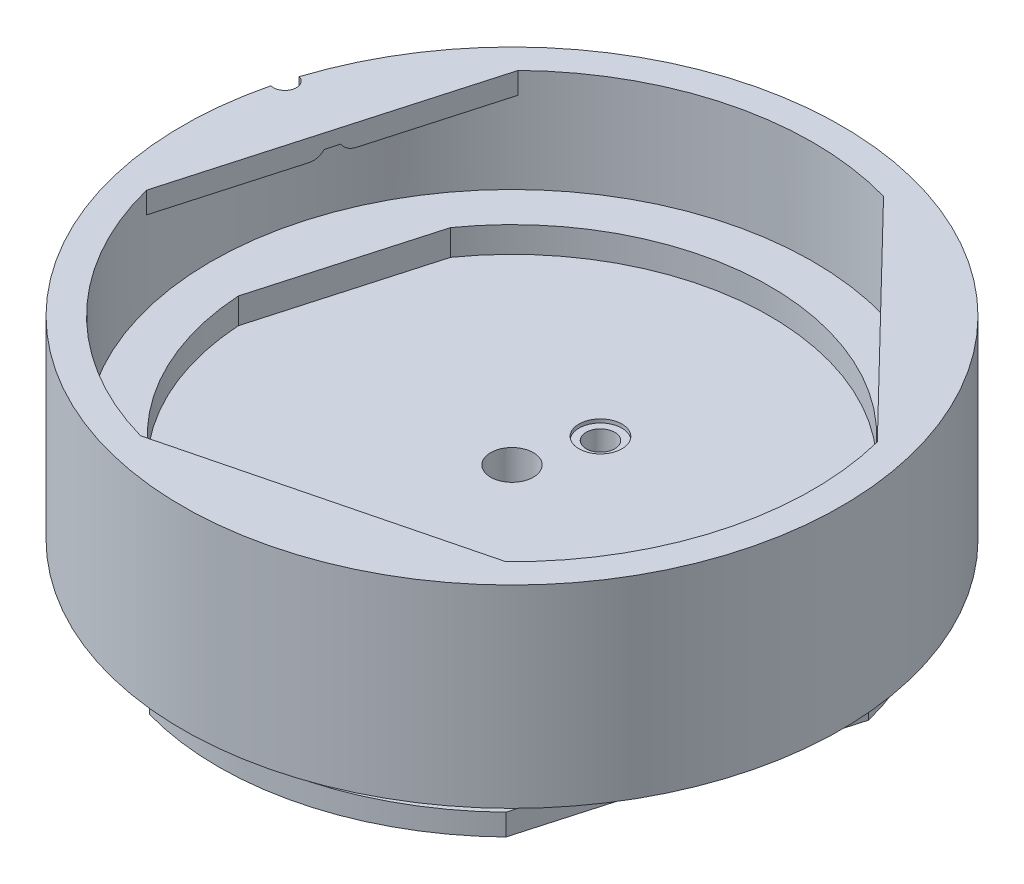
SolidWorks part; units mm, degrees
ref_plane "Front" through (0, 0, 0) normal (0, 0, 1) x (1, 0, 0)
ref_plane "Top" through (0, 0, 0) normal (0, 1, 0) x (1, 0, 0)
ref_plane "Right" through (0, 0, 0) normal (1, 0, 0) x (0, 0, -1)
sketch "Sketch1" plane through (0, 0, 0) normal (0, 1, 0) x (1, 0, 0)
  circle A0 centre (0, 0) radius 20.5
extrude "Boss-Extrude1" add sketch "Sketch1" along normal blind 1.5
sketch "Sketch2" plane through (0, 1.5, 0) normal (0, 1, 0) x (1, 0, 0)
  line L0 (-12.1923, 12.5538) -> (-12.889, 13.2712)
  line L1 (-16.9681, -4.2819) -> (-17.9377, -4.5266)
  line L2 (16.9681, 4.2819) -> (17.9377, 4.5266)
  line L3 (4.7758, 16.8357) -> (5.0487, 17.7978)
  line L4 (-4.7758, -16.8357) -> (-5.0487, -17.7978)
  line L5 (12.1923, -12.5538) -> (12.889, -13.2712)
  line L6 (-14.2824, 14.7059) -> (5.5945, 19.7219)
  line L7 (19.8769, 5.016) -> (14.2824, -14.7059)
  line L8 (-19.8769, -5.016) -> (-5.5945, -19.7219)
  line L9 (0, 0) -> (-14.2824, 14.7059) construction
  arc A0 (-19.8769, -5.016) -> (-5.5945, -19.7219) centre (0, 0) ccw
  arc A1 (-12.889, 13.2712) -> (-17.9377, -4.5266) centre (0, 0) ccw
  arc A2 (-12.1923, 12.5538) -> (-16.9681, -4.2819) centre (0, 0) ccw
  arc A3 (17.9377, 4.5266) -> (5.0487, 17.7978) centre (0, 0) ccw
  arc A4 (16.9681, 4.2819) -> (4.7758, 16.8357) centre (0, 0) ccw
  arc A5 (-5.0487, -17.7978) -> (12.889, -13.2712) centre (0, 0) ccw
  arc A6 (-4.7758, -16.8357) -> (12.1923, -12.5538) centre (0, 0) ccw
  arc A7 (14.2824, -14.7059) -> (19.8769, 5.016) centre (0, 0) ccw
  arc A8 (5.5945, 19.7219) -> (-14.2824, 14.7059) centre (0, 0) ccw
  point P13 (0, 0)
  dimension "D2" = 3
  dimension "D1" = 60
extrude "Cut-Extrude1" cut sketch "Sketch2" against normal blind 11
sketch "Sketch3" plane through (0, 1.5, 0) normal (0, 1, 0) x (1, 0, 0)
  circle A1 centre (0, 0) radius 17.5
extrude "Boss-Extrude2" add sketch "Sketch3" along normal blind 2
sketch "Sketch4" plane through (0, 3.5, 0) normal (0, 1, 0) x (1, 0, 0)
  circle A1 centre (0, 0) radius 23
extrude "Boss-Extrude3" add sketch "Sketch4" along normal blind 1
sketch "Sketch5" plane through (0, 4.5, 0) normal (0, 1, 0) x (1, 0, 0)
  circle A0 centre (0, 0) radius 23
  circle A1 centre (0, 0) radius 21
extrude "Boss-Extrude4" add sketch "Sketch5" along normal blind 11
sketch "Sketch6" plane through (0, 15.5, 0) normal (0, 1, 0) x (1, 0, 0)
  line L0 (0, 0) -> (-4.4043, 17.4529) construction
  line L2 (0, 0) -> (17.3168, -4.9122) construction
  line L5 (0, 0) -> (-12.9125, -12.5407) construction
  line L6 (14.6308, -15.0646) -> (-5.7309, -20.2029)
  line L7 (-20.3617, -5.1383) -> (-14.6308, 15.0646)
  line L8 (5.7309, 20.2029) -> (20.3617, 5.1383)
  circle A1 centre (0, 0) radius 23
  arc A4 (14.6308, -15.0646) -> (20.3617, 5.1383) centre (0, 0) ccw
  arc A5 (-20.3617, -5.1383) -> (-5.7309, -20.2029) centre (0, 0) ccw
  arc A6 (5.7309, 20.2029) -> (-14.6308, 15.0646) centre (0, 0) ccw
  point P14 (0, 0)
  point P18 (0, 0)
  point P22 (0, 0)
  dimension "D1" = 3
extrude "Boss-Extrude6" add sketch "Sketch6" along normal blind 1.5
sketch "Sketch7" plane through (0, 1.5, 0) normal (0, 1, 0) x (1, 0, 0)
  line L0 (0, 0) -> (4.2819, -16.9681) construction
  line L1 (4.0555, -18.05) -> (4.494, -20.0014)
  line L2 (4.9946, -17.813) -> (5.5346, -19.7388)
  arc A0 (-4.7758, -16.8357) -> (12.1923, -12.5538) centre (0, 0) ccw construction
  arc A1 (4.494, -20.0014) -> (5.5346, -19.7388) centre (0, 0) ccw
  arc A3 (4.0555, -18.05) -> (4.9946, -17.813) centre (0, 0) ccw
  dimension "D1" = 1.5
extrude "Boss-Extrude7" add sketch "Sketch7" along normal blind 0.8
fillet "Fillet3" radius 0.4 2 edges at (5.2646, 2.3, 18.7759) (4.2747, 2.3, 19.0257) first distance on face at (5.2646, 1.9, 18.7759) first distance on face at (4.2747, 1.9, 19.0257)
pattern_circular "CirPattern4" count 3 over 360 about axis through (0, 3.5, 0) along (0, 1, 0) of "Boss-Extrude7", "Fillet3"
ref_plane "Plane1" through (0, 15, 0) normal (0, 1, 0) x (1, 0, 0)
sketch "草图1" plane through (0, 17, 0) normal (0, 1, 0) x (1, 0, 0)
  line L0 (0, 0) -> (-12.5538, -12.1923) construction
  line L1 (0, 0) -> (-4.2819, 16.9681) construction
  line L2 (0, 0) -> (16.8357, -4.7758) construction
  circle A0 centre (0, 0) radius 18 construction
  circle A1 centre (0, 0) radius 17.5 construction
  circle A2 centre (0, 0) radius 18
  circle A3 centre (0, 0) radius 17
  point P9 (0, 0)
  dimension "D1" = 3
ref_plane "基准面1" through (0, 15, 0) normal (0, 1, 0) x (1, 0, 0)
sketch "草图9" plane through (0, 15, 0) normal (0, 1, 0) x (1, 0, 0)
  line L0 (0, 0) -> (5.016, -19.8769) construction
  line L3 (15.4424, 14.2314) -> (12.8687, 11.8595)
  line L4 (14.6764, 15.0201) -> (12.2303, 12.5167)
  arc A0 (4.494, -20.0014) -> (5.5346, -19.7388) centre (0, 0) ccw construction
  arc A5 (12.8687, 11.8595) -> (12.2303, 12.5167) centre (0, 0) ccw
  arc A6 (15.4424, 14.2314) -> (14.6764, 15.0201) centre (0, 0) ccw
  point P15 (0, 0)
extrude "切除-拉伸14" cut sketch "草图9" against normal blind 1 and the other way blind 1
fillet "圆角4" radius 1 2 edges at (14.4102, 15.5, -13.2802) (13.6954, 15.5, -14.0162)
pattern_circular "阵列(圆周)2" count 3 over 360 about axis through (0, 17, 0) along (0, 1, 0) of "切除-拉伸14", "圆角4"
sketch "草图15" plane through (0, 4.5, 0) normal (0, 1, 0) x (1, 0, 0)
  line L0 (0, 0) -> (-4.2819, 16.9681) construction
  circle A0 centre (0, 0) radius 21
extrude "凸台-拉伸6" add sketch "草图15" along normal blind 3.5
sketch "草图17" plane through (0, 8, 0) normal (0, 1, 0) x (1, 0, 0)
  circle A0 centre (0, 0) radius 1.49
extrude "切除-拉伸17" cut sketch "草图17" against normal blind 32
sketch "草图20" plane through (0, 8, 0) normal (0, 1, 0) x (1, 0, 0)
  circle A0 centre (0, 0) radius 21
  circle A1 centre (0, 0) radius 18
extrude "凸台-拉伸8" add sketch "草图20" along normal blind 1.8
sketch "草图21" plane through (0, 8, 0) normal (0, 1, 0) x (1, 0, 0)
  line L0 (0, 0) -> (16.6631, -4.7268) construction
  line L2 (0, 0) -> (-7.1059, -25.0502) construction
  circle A6 centre (0, 0) radius 1.49 construction
  circle A7 centre (1.4334, -0.4066) radius 0.5 construction
  circle A8 centre (0, 0) radius 17.5 construction
  circle A9 centre (0, 0) radius 11 construction
  circle A10 centre (0, 0) radius 16 construction
  circle A11 centre (15.3927, -4.3664) radius 1.5
  circle A12 centre (0, 0) radius 5 construction
  circle A14 centre (1.3645, 4.8102) radius 1.5
extrude "切除-拉伸18" cut sketch "草图21" against normal blind 0.25
sketch "草图22" plane through (0, 7.75, 0) normal (0, 1, 0) x (1, 0, 0)
  line L0 (0, 0) -> (16.9497, -4.8081) construction
  circle A7 centre (15.3927, -4.3664) radius 1
  circle A8 centre (1.3645, 4.8102) radius 1
extrude "切除-拉伸19" cut sketch "草图22" against normal blind 10
sketch "草图23" plane through (0, 8, 0) normal (0, 1, 0) x (1, 0, 0)
  line L1 (0, 0) -> (-1.4334, 0.4066) construction
  line L2 (0, 0) -> (-2.4482, -8.6305) construction
  line L3 (-14.689, 10.4035) -> (-17.9638, -1.141)
  circle A2 centre (-15.6614, -2.1579) radius 1.5 construction
  circle A7 centre (-12.1955, 10.06) radius 1.5 construction
  arc A8 (-14.689, 10.4035) -> (-17.9638, -1.141) centre (0, 0) ccw
  dimension "D1" = 6.35
  dimension "D2" = 14.478
sketch "草图24" plane through (0, 17, 0) normal (0, 1, 0) x (1, 0, 0)
  line L0 (0, 0) -> (-17.4962, 4.9631) construction
  circle A0 centre (-22.127, 6.2767) radius 0.8
  circle A1 centre (0, 0) radius 23 construction
extrude "切除-拉伸20" cut sketch "草图24" against normal blind 18
extrude "凸台-拉伸9" add sketch "草图23" along normal blind 1.8 contours L3 A8
equation "\"1.810.00mm\"=10"
